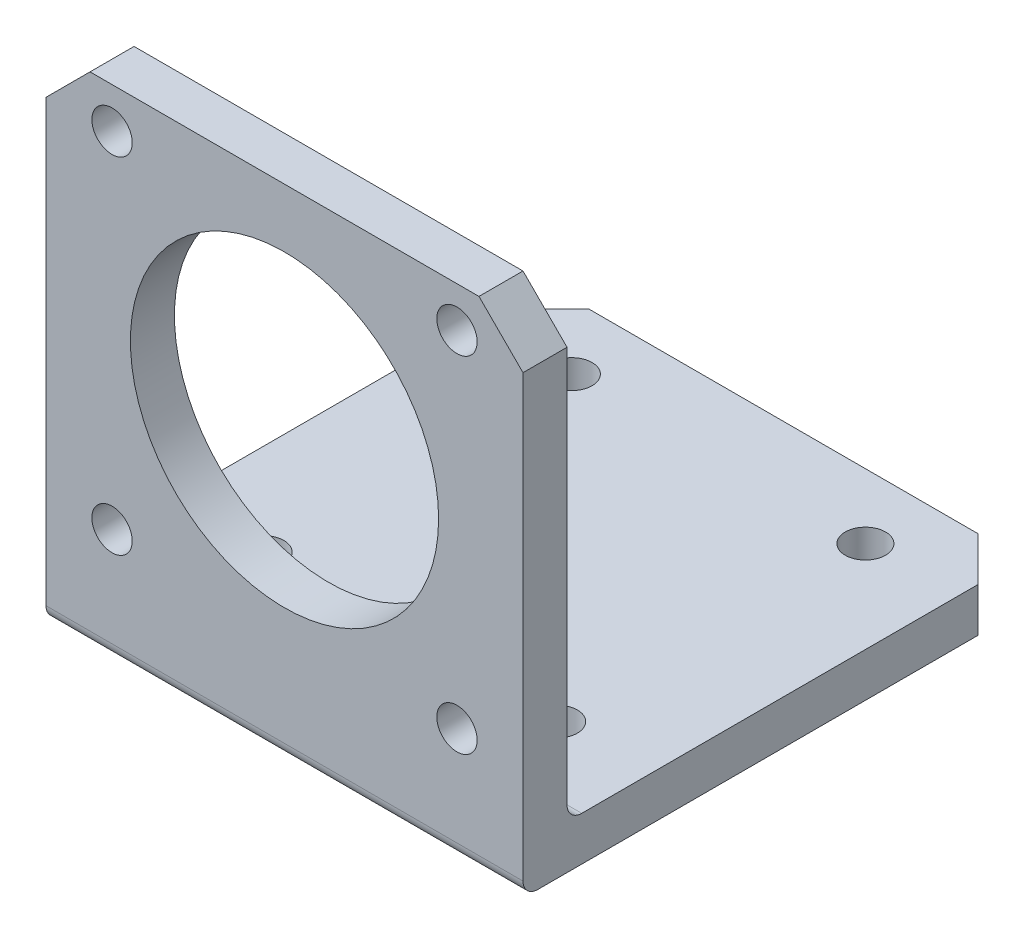
SolidWorks part; units mm, degrees
ref_plane "前视基准面" through (0, 0, 0) normal (0, 0, 1) x (1, 0, 0)
ref_plane "上视基准面" through (0, 0, 0) normal (0, 1, 0) x (1, 0, 0)
ref_plane "右视基准面" through (0, 0, 0) normal (1, 0, 0) x (0, 0, -1)
sketch "草图1" plane through (0, 0, 0) normal (0, 0, 1) x (1, 0, 0)
  line L1 (-28.9531, 50.5797) -> (36.0469, 50.5797)
  line L2 (-28.9531, 50.5797) -> (-28.9531, -17.4203)
  line L3 (-28.9531, -17.4203) -> (36.0469, -17.4203)
  line L4 (36.0469, 50.5797) -> (36.0469, -17.4203)
  circle A0 centre (3.5469, 21.5797) radius 21
  dimension "D3" = 42
  dimension "D4" = 39
  dimension "D1" = 68
  dimension "D2" = 65
extrude "凸台-拉伸1" add sketch "草图1" along normal blind 6
sketch "草图3" plane through (36.0469, 0, 0) normal (1, 0, 0) x (0, 0, -1)
  line L0 (0, -11.4203) -> (62, -11.4203)
  line L2 (62, -11.4203) -> (62, -17.4203)
  line L3 (62, -17.4203) -> (0, -17.4203)
  line L4 (-6, -17.4203) -> (-6, 50.5797) construction
  line L5 (0, -11.4203) -> (0, -17.4203)
  dimension "D1" = 68
  dimension "D2" = 6
extrude "凸台-拉伸2" add sketch "草图3" against normal blind 65
chamfer "倒角2" distance 6 angle 45 1 edges at (36.0469, -14.4203, -62)
chamfer "倒角3" distance 6 angle 45 1 edges at (-28.9531, -14.4203, -62)
chamfer "倒角4" distance 6 angle 45 1 edges at (-28.9531, 50.5797, 3)
chamfer "倒角5" distance 6 angle 45 1 edges at (36.0469, 50.5797, 3)
fillet "圆角1" radius 2 1 edges at (3.5469, -17.4203, 6)
fillet "圆角2" radius 2 1 edges at (3.5469, -11.4203, 0)
sketch "草图5" plane through (0, 0, 0) normal (0, 0, -1) x (-1, 0, 0)
  line L0 (-3.5469, 50.5797) -> (-3.5469, -49949.4203) construction
  line L1 (-30.0469, 50.5797) -> (22.9531, 50.5797) construction
  line L2 (-36.0469, -9.4203) -> (28.9531, -9.4203) construction
  line L3 (-22.6469, 21.5797) -> (15.5531, 21.5797) construction
  circle A0 centre (-27.0469, 45.0797) radius 2.75
  circle A1 centre (19.9531, 45.0797) radius 2.75
  circle A3 centre (19.9531, -1.9203) radius 2.75
  circle A4 centre (-27.0469, -1.9203) radius 2.75
  point P4 (-3.5469, 50.5797)
  point P7 (-3.5469, -9.4203)
  dimension "D1" = 5.5
  dimension "D2" = 23.5
  dimension "D3" = 47
extrude "切除-拉伸3" cut sketch "草图5" against normal through all
sketch "草图6" plane through (0, -11.4203, 0) normal (0, 1, 0) x (1, 0, 0)
  line L0 (3.5469, 2) -> (3.5469, 50002) construction
  line L1 (-28.9531, 2) -> (36.0469, 2) construction
  line L2 (-22.9531, 62) -> (30.0469, 62) construction
  circle A0 centre (23.5469, 11.1568) radius 2.75
  circle A1 centre (23.5469, 53.1568) radius 2.75
  circle A2 centre (-16.4531, 53.1568) radius 2.75
  circle A3 centre (-16.4531, 11.1568) radius 2.75
  point P4 (3.5469, 2)
  point P7 (3.5469, 62)
  dimension "D1" = 5.5
  dimension "D3" = 5.5
  dimension "D2" = 20
  dimension "D4" = 42
  dimension "D5" = 20
extrude "切除-拉伸4" cut sketch "草图6" against normal through all
ref_axis "基准轴2" through (3.5469, 21.5797, 48.3803) along (0, 0, -1)
